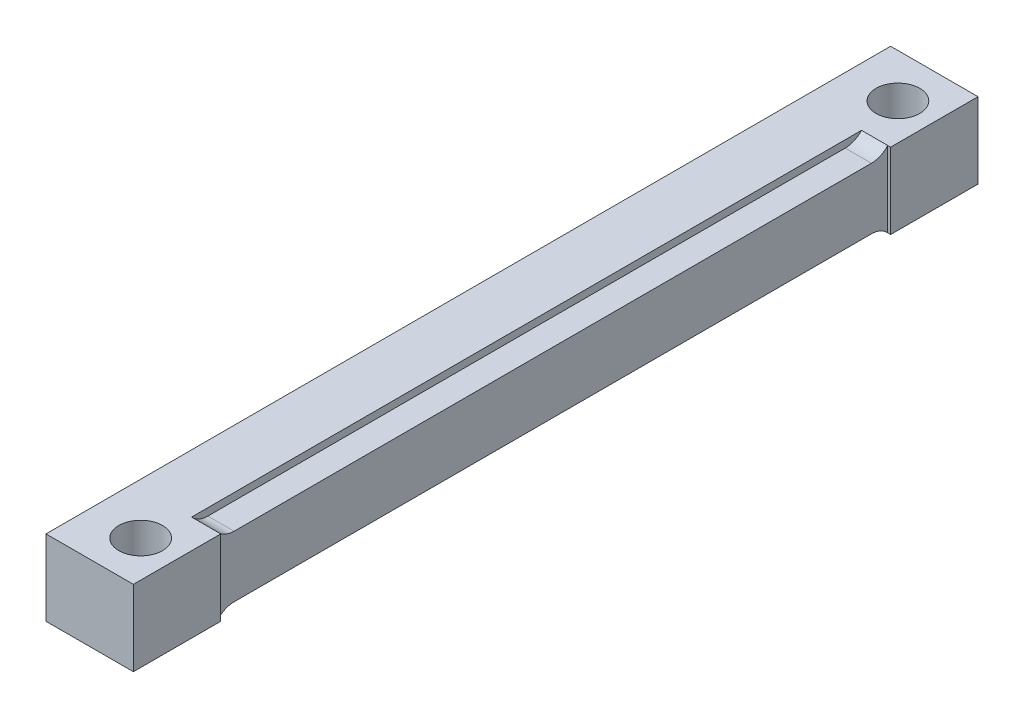
SolidWorks part; units mm, degrees
ref_plane "Front Plane" through (0, 0, 0) normal (0, 0, 1) x (1, 0, 0)
ref_plane "Top Plane" through (0, 0, 0) normal (0, 1, 0) x (1, 0, 0)
ref_plane "Right Plane" through (0, 0, 0) normal (1, 0, 0) x (0, 0, -1)
sketch "Sketch1" plane through (0, 0, 0) normal (0, 1, 0) x (1, 0, 0)
  line L0 (0, 0) -> (6, 0)
  line L1 (6, 0) -> (6, 58)
  line L2 (6, 58) -> (0, 58)
  line L5 (0, 58) -> (0, 0)
  dimension "D1" = 58
  dimension "D2" = 6
extrude "Boss-Extrude1" add sketch "Sketch1" along normal blind 5.2
sketch "Sketch3" plane through (0, 5.2, 0) normal (0, 1, 0) x (1, 0, 0)
  line L0 (0, 0) -> (6, 0) construction
  line L1 (6, 58) -> (0, 58) construction
  line L2 (6, 0) -> (6, 58) construction
  circle A0 centre (3.5, 55) radius 1.5
  circle A1 centre (3.5, 3) radius 1.5
  dimension "D1" = 3
  dimension "D2" = 3
  dimension "D3" = 3
  dimension "D4" = 2.5
extrude "Cut-Extrude2" cut sketch "Sketch3" against normal up to next
sketch "Sketch4" plane through (6, 0, 0) normal (1, 0, 0) x (0, 0, -1)
  line L0 (0, 5.2) -> (58, 5.2) construction
  line L1 (6, 5.2) -> (52, 5.2)
  line L2 (6, 5.2) -> (6, 4.7)
  line L3 (6, 4.7) -> (52, 4.7)
  line L4 (52, 5.2) -> (52, 4.7)
  line L5 (0, 0) -> (58, 0) construction
  line L6 (6, 0) -> (52, 0)
  line L7 (6, 0) -> (6, 0.5)
  line L8 (6, 0.5) -> (52, 0.5)
  line L9 (52, 0) -> (52, 0.5)
  line L10 (0, 5.2) -> (0, 0) construction
  line L11 (58, 5.2) -> (58, 0) construction
  dimension "D1" = 0.5
  dimension "D2" = 0.5
  dimension "D3" = 6
  dimension "D4" = 6
extrude "Cut-Extrude3" cut sketch "Sketch4" against normal blind 2
fillet "Fillet1" radius 1.5 4 edges at (5, 0.5, -52) (5, 0.5, -6) (5, 4.7, -6) (5, 4.7, -52)
sketch "Sketch5" plane through (6, 0, 0) normal (1, 0, 0) x (0, 0, -1)
  line L0 (0, 5.2) -> (6, 5.2) construction
  line L1 (6, 5.2) -> (52, 5.2)
  line L2 (6, 5.2) -> (6, 0)
  line L3 (6, 0) -> (52, 0)
  line L4 (52, 5.2) -> (52, 0)
  line L5 (52, 0) -> (58, 0) construction
  line L6 (0, 5.2) -> (0, 0) construction
  line L7 (58, 5.2) -> (58, 0) construction
  dimension "D1" = 6
  dimension "D2" = 6
extrude "Cut-Extrude4" cut sketch "Sketch5" against normal blind 0.2
